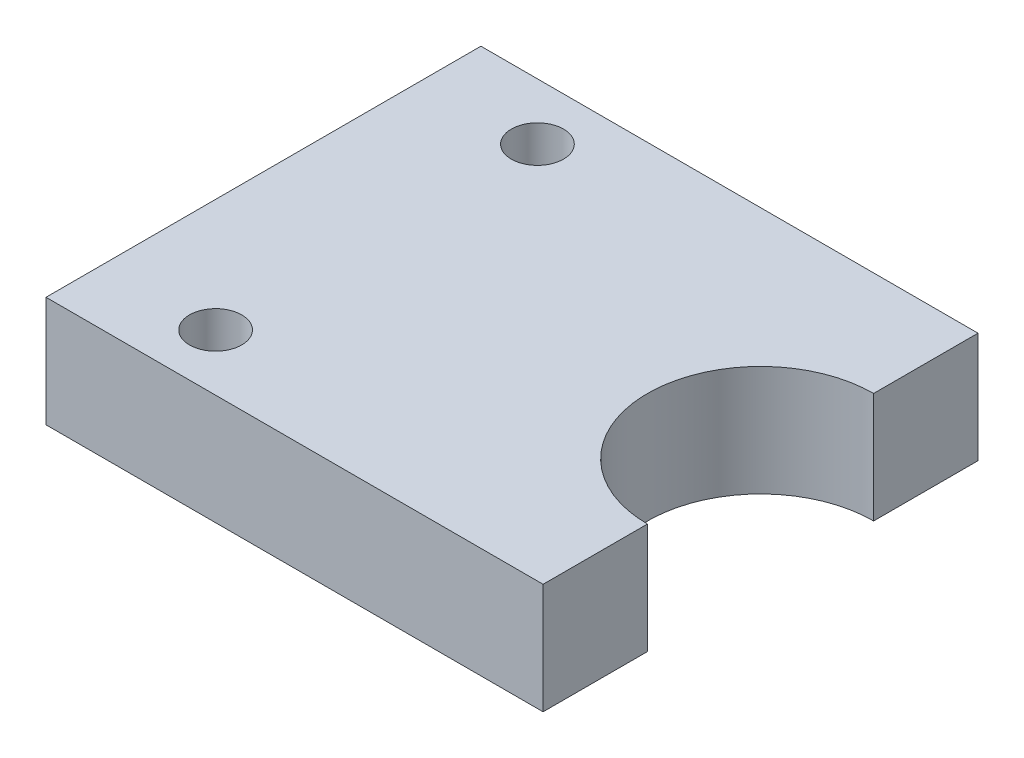
SolidWorks part; units mm, degrees
material "Aleación 6061"
ref_plane "Alzado" through (0, 0, 0) normal (0, 0, 1) x (1, 0, 0)
ref_plane "Planta" through (0, 0, 0) normal (0, 1, 0) x (1, 0, 0)
ref_plane "Vista lateral" through (0, 0, 0) normal (1, 0, 0) x (0, 0, -1)
sketch "Croquis2" plane through (0, 0, 0) normal (0, 1, 0) x (1, 0, 0)
  line L0 (0, 25) -> (-57.15, 25)
  line L4 (-57.15, 25) -> (-57.15, -25)
  line L8 (0, -25) -> (0, -13)
  line L9 (0, 13) -> (0, 25)
  line L11 (0, -25) -> (-57.15, -25)
  line L12 (0, 32.9631) -> (0, -34.8375) construction
  circle A0 centre (-44.15, -18.5) radius 3
  arc A2 (0, 13) -> (0, -13) centre (0, 0) ccw
  circle A5 centre (-44.15, 18.5) radius 3
  point P0 (0, 0)
  point P2 (0, 0)
  point P3 (0, 0)
  dimension "D3" = 25
  dimension "D4" = 13
  dimension "D6" = 6
  dimension "D7" = 6
  dimension "D9" = 13
  dimension "D1" = 50
  dimension "D2" = 57.15
extrude "Saliente-Extruir1" add sketch "Croquis2" along normal blind 12.7
